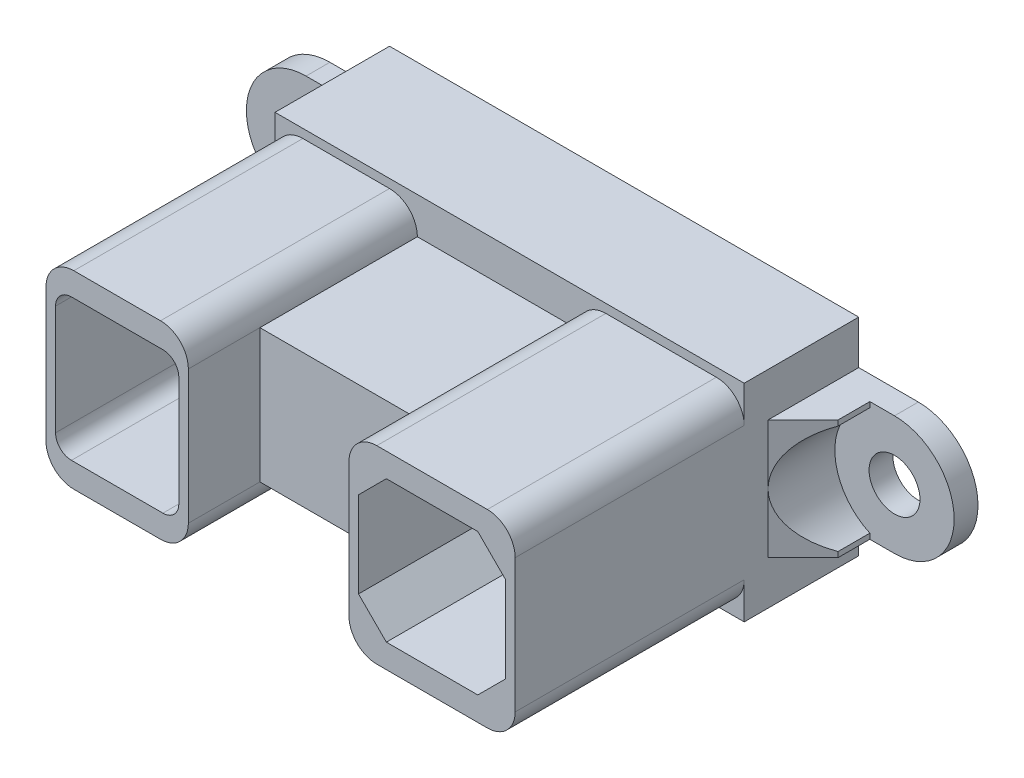
SolidWorks part; units mm, degrees
material "PUR"
ref_plane "Front Plane" through (0, 0, 0) normal (0, 0, 1) x (1, 0, 0)
ref_plane "Top Plane" through (0, 0, 0) normal (0, 1, 0) x (1, 0, 0)
ref_plane "Right Plane" through (0, 0, 0) normal (1, 0, 0) x (0, 0, -1)
sketch "Sketch1" plane through (0, 0, 0) normal (0, 0, 1) x (1, 0, 0)
  line L0 (18.5, 0) -> (-18.5, 0) construction
  line L1 (-14.75, -6.5) -> (14.75, -6.5)
  line L2 (-14.75, -6.5) -> (-14.75, 6.5) construction
  line L3 (-14.75, 6.5) -> (14.75, 6.5)
  line L4 (14.75, -6.5) -> (14.75, 6.5) construction
  line L5 (-14.75, -6.5) -> (14.75, 6.5) construction
  line L6 (-14.75, 6.5) -> (14.75, -6.5) construction
  line L7 (-18.5, 3.75) -> (-18.5, -3.75) construction
  line L8 (18.5, 3.75) -> (18.5, -3.75) construction
  line L9 (-18.5, 3.75) -> (-14.75, 3.75)
  line L10 (-14.75, 3.75) -> (-14.75, 6.5)
  line L11 (-18.5, -3.75) -> (-14.75, -3.75)
  line L12 (-14.75, -3.75) -> (-14.75, -6.5)
  line L13 (18.5, 3.75) -> (14.75, 3.75)
  line L14 (14.75, 3.75) -> (14.75, 6.5)
  line L15 (18.5, -3.75) -> (14.75, -3.75)
  line L16 (14.75, -3.75) -> (14.75, -6.5)
  circle A0 centre (18.5, 0) radius 1.6
  circle A1 centre (-18.5, 0) radius 1.6
  arc A2 (-18.5, 3.75) -> (-18.5, -3.75) centre (-18.5, 0) ccw
  arc A3 (18.5, 3.75) -> (18.5, -3.75) centre (18.5, 0) cw
  point P0 (0, 0)
  point P9 (0, 0)
  point P14 (-18.5, 0)
  point P17 (18.5, 0)
  dimension "D4" = 3.2
  dimension "D5" = 3.2
  dimension "D1" = 13
  dimension "D2" = 29.5
  dimension "D3" = 37
  dimension "D6" = 7.5
  dimension "D7" = 7.5
extrude "Boss-Extrude1" add sketch "Sketch1" along normal blind 7.2 contours A3 L13 L14 L3 L10 L9 A2 L11 L12 L1 L16 L15 A1 A0 region at (0, 0, 0)
sketch "Sketch2" plane through (0, 0, 7.2) normal (0, 0, 1) x (1, 0, 0)
  circle A1 centre (-18.5, 0) radius 3.75
  circle A2 centre (18.5, 0) radius 3.75
extrude "Cut-Extrude1" cut sketch "Sketch2" against normal blind 5.7
sketch "Sketch4" plane through (0, -3.75, 0) normal (0, -1, 0) x (1, 0, 0)
  line L0 (-18.5, 1.5) -> (-16.95, 1.5)
  line L1 (-16.95, 1.5) -> (-16.95, 3.5)
  line L2 (-14.75, 7.2) -> (-14.75, 5.7)
  line L3 (-14.75, 7.2) -> (-14.75, 0) construction
  line L4 (-16.95, 3.5) -> (-14.75, 5.7)
  line L5 (-14.75, 7.2) -> (-14.75, 0) construction
  line L6 (-18.5, 1.5) -> (-18.5, 7.2)
  line L7 (-18.5, 7.2) -> (-14.75, 7.2)
  line L8 (18.5, 1.5) -> (16.95, 1.5)
  line L9 (20.1, 1.5) -> (16.9, 1.5) construction
  line L10 (16.95, 1.5) -> (16.95, 3.5)
  line L11 (14.75, 7.2) -> (14.75, 5.7)
  line L12 (14.75, 7.2) -> (14.75, 0) construction
  line L13 (14.75, 5.7) -> (16.95, 3.5)
  line L14 (14.75, 7.2) -> (18.5, 7.2)
  line L15 (18.5, 7.2) -> (18.5, 1.5)
  dimension "D1" = 2
  dimension "D2" = 1.5
  dimension "D3" = 45
  dimension "D4" = 2
  dimension "D5" = 1.5
  dimension "D6" = 45
extrude "Cut-Extrude2" cut sketch "Sketch4" against normal up to surface (7.5 mm away) up to face at (-17, 3.75, 3.18)
sketch "Sketch5" plane through (0, 0, 7.2) normal (0, 0, 1) x (1, 0, 0)
  line L0 (-14.75, 0) -> (-10.275, 0) construction
  line L1 (-14.75, -6.5) -> (-14.75, 6.5) construction
  line L2 (-10.275, 0) -> (9.525, 0) construction
  line L3 (14.75, -6.5) -> (14.75, 6.5) construction
  line L4 (-5.8, -5.95) -> (-14.75, -5.95)
  line L5 (-5.8, -5.95) -> (-5.8, 5.95) construction
  line L6 (-5.8, 5.95) -> (-14.75, 5.95)
  line L7 (-14.75, -5.95) -> (-14.75, 5.95)
  line L8 (-5.8, -5.95) -> (-14.75, 5.95) construction
  line L9 (-5.8, 5.95) -> (-14.75, -5.95) construction
  line L10 (-14.15, -4.45) -> (-6.4, -4.45)
  line L11 (-14.15, -4.45) -> (-14.15, 4.45)
  line L12 (-14.15, 4.45) -> (-6.4, 4.45)
  line L13 (-6.4, -4.45) -> (-6.4, 4.45)
  line L14 (-14.15, -4.45) -> (-6.4, 4.45) construction
  line L15 (-14.15, 4.45) -> (-6.4, -4.45) construction
  line L16 (4.3, -5.95) -> (14.75, -5.95)
  line L17 (4.3, -5.95) -> (4.3, 5.95) construction
  line L18 (4.3, 5.95) -> (14.75, 5.95)
  line L19 (14.75, -5.95) -> (14.75, 5.95)
  line L20 (4.3, -5.95) -> (14.75, 5.95) construction
  line L21 (4.3, 5.95) -> (14.75, -5.95) construction
  line L22 (0, 4.2) -> (0, -4.2) construction
  line L23 (4.9, -4.45) -> (14.15, -4.45)
  line L24 (4.9, -4.45) -> (4.9, 4.45)
  line L25 (4.9, 4.45) -> (14.15, 4.45)
  line L26 (14.15, -4.45) -> (14.15, 4.45)
  line L27 (4.9, -4.45) -> (14.15, 4.45) construction
  line L28 (4.9, 4.45) -> (14.15, -4.45) construction
  line L29 (0, -4.2) -> (-5.8, -4.2)
  line L30 (0, -4.2) -> (4.3, -4.2)
  line L31 (0, 4.2) -> (-5.8, 4.2)
  line L32 (0, 4.2) -> (4.3, 4.2)
  line L33 (-5.8, 4.2) -> (-5.8, 5.95)
  line L34 (-5.8, -4.2) -> (-5.8, -5.95)
  line L35 (4.3, -4.2) -> (4.3, -5.95)
  line L36 (4.3, 4.2) -> (4.3, 5.95)
  point P27 (0, 0)
  dimension "D1" = 4.475
  dimension "D2" = 19.8
  dimension "D3" = 11.9
  dimension "D5" = 0.6
  dimension "D4" = 1.5
  dimension "D6" = 11.9
  dimension "D7" = 0.6
  dimension "D8" = 1.5
  dimension "D9" = 8.4
extrude "Boss-Extrude2" add sketch "Sketch5" along normal blind 14.4
sketch "Sketch6" plane through (0, 0, 21.6) normal (0, 0, 1) x (1, 0, 0)
  line L1 (-5.8, 4.2) -> (4.3, 4.2)
  line L2 (-5.8, 4.2) -> (-5.8, -4.2)
  line L3 (-5.8, -4.2) -> (4.3, -4.2)
  line L4 (4.3, 4.2) -> (4.3, -4.2)
extrude "Cut-Extrude3" cut sketch "Sketch6" against normal blind 4.5
fillet "Fillet1" radius 1.75 8 edges at (4.3, 5.95, 14.4) (14.75, 5.95, 14.4) (14.75, -5.95, 14.4) (4.3, -5.95, 14.4) (-5.8, 5.95, 14.4) (-14.75, 5.95, 14.4) (-14.75, -5.95, 14.4) (-5.8, -5.95, 14.4)
fillet "Fillet2" radius 1 4 edges at (-14.15, -4.45, 14.4) (-6.4, -4.45, 14.4) (-14.15, 4.45, 14.4) (-6.4, 4.45, 14.4)
chamfer "Chamfer1" distance 1.75 angle 45 4 edges at (4.9, -4.45, 14.4) (14.15, -4.45, 14.4) (14.15, 4.45, 14.4) (4.9, 4.45, 14.4)
sketch "Sketch7" plane through (0, 0, 0) normal (0, 0, -1) x (-1, 0, 0)
  line L0 (14, -5.75) -> (14, 5.75)
  line L1 (14.75, -6.5) -> (-14.75, -6.5) construction
  line L2 (14.75, -6.5) -> (14.75, 6.5) construction
  line L3 (14.75, 6.5) -> (-14.75, 6.5) construction
  line L4 (-14.75, -6.5) -> (-14.75, 6.5) construction
  line L5 (14, 5.75) -> (-14, 5.75)
  line L6 (-14, -5.75) -> (-14, 5.75)
  line L7 (14, -5.75) -> (-14, -5.75) construction
  line L8 (0, -5.75) -> (0, -6.5) construction
  line L9 (5.05, -5.75) -> (5.05, -6.5)
  line L10 (5.05, -6.5) -> (-5.05, -6.5)
  line L11 (-5.05, -6.5) -> (-5.05, -5.75)
  line L12 (5.05, -5.75) -> (14, -5.75)
  line L13 (-5.05, -5.75) -> (-14, -5.75)
  dimension "D2" = 10.1
  dimension "D1" = 0.75
extrude "Cut-Extrude4" cut sketch "Sketch7" against normal blind 3.3
sketch "Sketch8" plane through (0, 0, 3.3) normal (0, 0, -1) x (-1, 0, 0)
  line L1 (5.05, -6.5) -> (-5.05, -6.5)
  line L2 (5.05, -6.5) -> (5.05, -5.75)
  line L3 (5.05, -5.75) -> (-5.05, -5.75)
  line L4 (-5.05, -6.5) -> (-5.05, -5.75)
extrude "Cut-Extrude5" cut sketch "Sketch8" against normal up to next
sketch "Sketch9" plane through (0, -5.75, 0) normal (0, -1, 0) x (1, 0, 0)
  line L0 (5.05, 7.2) -> (5.05, 3.3) construction
  line L1 (-5.05, 3.3) -> (5.05, 3.3)
  line L2 (-5.05, 3.3) -> (-5.05, 4.5)
  line L3 (-5.05, 4.5) -> (5.05, 4.5)
  line L4 (5.05, 3.3) -> (5.05, 4.5)
  dimension "D1" = 1.2
extrude "Boss-Extrude3" add sketch "Sketch9" along normal blind 5.5
ref_point "Point1"
ref_axis "Axis1" through (-10.275, 0, 7.2) along (0, 0, 1)
equation "\"D4@Sketch1\"=\"D5@Sketch1\""
equation "\"D7@Sketch1\"=\"D6@Sketch1\""
equation "\"D4@Sketch4\"=\"D1@Sketch4\""
equation "\"D5@Sketch4\"=\"D2@Sketch4\""
equation "\"D6@Sketch4\"=\"D3@Sketch4\""
equation "\"D6@Sketch5\"=\"D3@Sketch5\""
equation "\"D7@Sketch5\"=\"D5@Sketch5\""
equation "\"D8@Sketch5\"=\"D4@Sketch5\""
